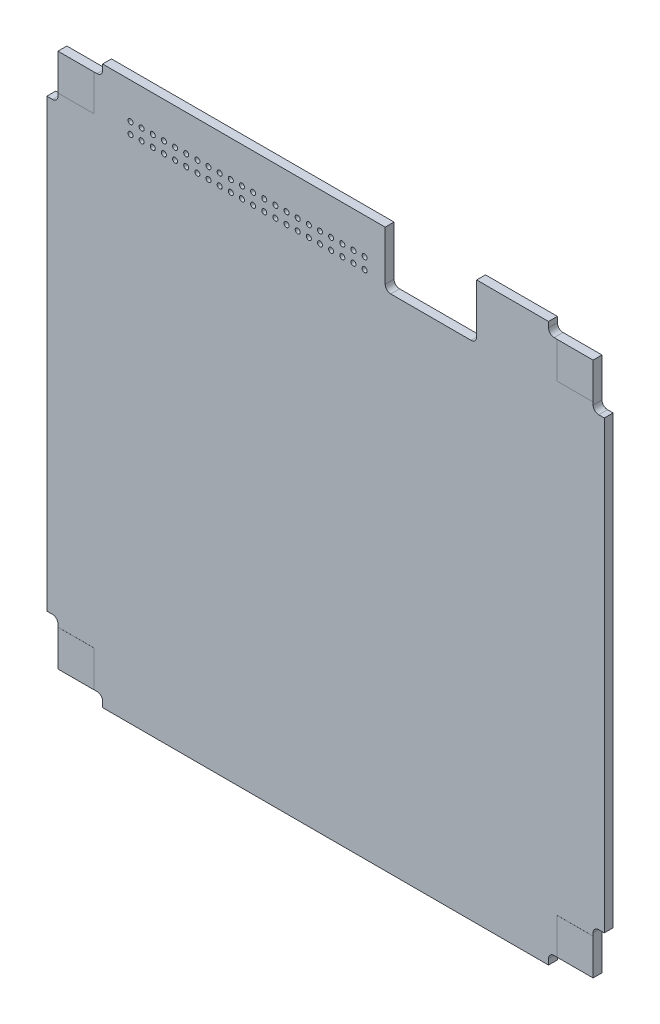
SolidWorks part; units mm, degrees
material "ABS"
ref_plane "Front Plane" through (0, 0, 0) normal (0, 0, 1) x (1, 0, 0)
ref_plane "Top Plane" through (0, 0, 0) normal (0, 1, 0) x (1, 0, 0)
ref_plane "Right Plane" through (0, 0, 0) normal (1, 0, 0) x (0, 0, -1)
sketch "Sketch1" plane through (0, 0, 0) normal (0, 0, 1) x (1, 0, 0)
  line L0 (-40, 50) -> (-40, 48)
  line L1 (-50, -50) -> (50, -50)
  line L2 (-50, -50) -> (-50, 50)
  line L3 (-50, 50) -> (50, 50)
  line L4 (50, -50) -> (50, 50)
  line L5 (-50, -50) -> (50, 50) construction
  line L6 (-50, 50) -> (50, -50) construction
  line L7 (-50, 50) -> (-40, 50)
  line L8 (-50, 50) -> (-50, 40)
  line L9 (-40, 48) -> (-48, 48)
  line L10 (-48, 48) -> (-48, 40)
  line L11 (50, 50) -> (40, 50)
  line L12 (50, 50) -> (50, 40)
  line L13 (-48, 40) -> (-50, 40)
  line L14 (50, 40) -> (48, 40)
  line L15 (-50, -50) -> (-37.8649, -50)
  line L16 (-50, -50) -> (-50, -37.8649)
  line L17 (50, 50) -> (50, 40)
  line L18 (50, 50) -> (40, 50)
  line L19 (50, -50) -> (41.5, -50)
  line L20 (50, -50) -> (50, -41.5)
  line L21 (48, 40) -> (48, 48)
  line L22 (48, 48) -> (40, 48)
  line L23 (40, 48) -> (40, 50)
  line L24 (40, -50) -> (40, -48)
  line L25 (50, -50) -> (40, -50)
  line L26 (50, -50) -> (50, -40)
  line L27 (40, -48) -> (48, -48)
  line L28 (48, -48) -> (48, -40)
  line L29 (48, -40) -> (50, -40)
  line L30 (-50, -40) -> (-48, -40)
  line L31 (-50, -50) -> (-50, -40)
  line L32 (-50, -50) -> (-40, -50)
  line L33 (-48, -40) -> (-48, -48)
  line L34 (-48, -48) -> (-40, -48)
  line L35 (-40, -48) -> (-40, -50)
  point P0 (0, 0)
  point P38 (0, 0)
  dimension "D1" = 100
  dimension "D2" = 100
  dimension "D3" = 2
  dimension "D4" = 10
  dimension "D5" = 4
extrude "Boss-Extrude1" add sketch "Sketch1" along normal blind 1.5875 contours L1 L4 L3 L2 region at (0, 0, 0)
fillet "Fillet1" radius 1 8 edges at (-48, -40, 0.7937) (-40, -48, 0.7937) (40, -48, 0.7937) (48, -40, 0.7937) (48, 40, 0.7937) (40, 48, 0.7937) (-40, 48, 0.7937) (-48, 40, 0.7937)
sketch "Sketch2" plane through (0, 0, 1.5875) normal (0, 0, 1) x (1, 0, 0)
  line L0 (0, 50) -> (0, -50) construction
  line L1 (-40, 50) -> (40, 50) construction
  line L2 (-40, -50) -> (40, -50) construction
  line L4 (-36, 45.8) -> (8, 45.8) construction
  line L5 (-36, 45.8) -> (-36, 43.55) construction
  line L6 (-36, 43.55) -> (8, 43.55) construction
  line L7 (8, 45.8) -> (8, 43.55) construction
  line L8 (-36, 50) -> (8, 50) construction
  line L9 (-36, 50) -> (-36, 45.8) construction
  line L10 (-36, 45.8) -> (8, 45.8) construction
  line L11 (8, 50) -> (8, 45.8) construction
  circle A0 centre (-35, 43.55) radius 0.45
  circle A1 centre (-33, 43.55) radius 0.45
  circle A2 centre (-31, 43.55) radius 0.45
  circle A3 centre (-29, 43.55) radius 0.45
  circle A4 centre (-27, 43.55) radius 0.45
  circle A5 centre (-25, 43.55) radius 0.45
  circle A6 centre (-23, 43.55) radius 0.45
  circle A7 centre (-21, 43.55) radius 0.45
  circle A8 centre (-19, 43.55) radius 0.45
  circle A9 centre (-17, 43.55) radius 0.45
  circle A10 centre (-15, 43.55) radius 0.45
  circle A11 centre (-13, 43.55) radius 0.45
  circle A12 centre (-11, 43.55) radius 0.45
  circle A13 centre (-9, 43.55) radius 0.45
  circle A14 centre (-7, 43.55) radius 0.45
  circle A15 centre (-5, 43.55) radius 0.45
  circle A16 centre (-3, 43.55) radius 0.45
  circle A17 centre (-1, 43.55) radius 0.45
  circle A18 centre (1, 43.55) radius 0.45
  circle A19 centre (3, 43.55) radius 0.45
  circle A20 centre (5, 43.55) radius 0.45
  circle A21 centre (7, 43.55) radius 0.45
  circle A22 centre (-33, 41.55) radius 0.45
  circle A23 centre (-31, 41.55) radius 0.45
  circle A24 centre (-29, 41.55) radius 0.45
  circle A25 centre (-27, 41.55) radius 0.45
  circle A26 centre (-25, 41.55) radius 0.45
  circle A27 centre (-23, 41.55) radius 0.45
  circle A28 centre (-21, 41.55) radius 0.45
  circle A29 centre (-19, 41.55) radius 0.45
  circle A30 centre (-17, 41.55) radius 0.45
  circle A31 centre (-15, 41.55) radius 0.45
  circle A32 centre (-13, 41.55) radius 0.45
  circle A33 centre (-11, 41.55) radius 0.45
  circle A34 centre (-9, 41.55) radius 0.45
  circle A35 centre (-7, 41.55) radius 0.45
  circle A36 centre (-5, 41.55) radius 0.45
  circle A37 centre (-3, 41.55) radius 0.45
  circle A38 centre (-1, 41.55) radius 0.45
  circle A39 centre (1, 41.55) radius 0.45
  circle A40 centre (3, 41.55) radius 0.45
  circle A41 centre (5, 41.55) radius 0.45
  circle A42 centre (7, 41.55) radius 0.45
  circle A43 centre (-35, 41.55) radius 0.45
  dimension "D1" = 0.9
  dimension "D6" = 15
  dimension "D4" = 42
  dimension "D5" = 2
  dimension "D7" = 2.25
  dimension "D8" = 44
  dimension "D10" = 1
  dimension "D11" = 4.2
  dimension "D2" = 22
  dimension "D3" = 2
extrude "Cut-Extrude1" cut sketch "Sketch2" against normal through all
sketch "Sketch3" plane through (0, 50, 0) normal (0, 1, 0) x (1, 0, 0)
  line L0 (-40, 0) -> (40, 0) construction
  line L1 (10.7, 0) -> (19.7, 0)
  line L2 (10.7, 0) -> (10.7, -1.5875)
  line L3 (10.7, -1.5875) -> (19.7, -1.5875)
  line L5 (-40, -1.5875) -> (40, -1.5875) construction
  line L6 (15.2, 0) -> (15.2, -1.5875) construction
  line L7 (12, 0) -> (12, -1.5875) construction
  line L8 (18.4, 0) -> (18.4, -1.5875) construction
  line L9 (-40, -1.5875) -> (40, -1.5875) construction
  line L10 (7, 0) -> (7, -1.5875) construction
  line L11 (6.55, -1.5875) -> (7.45, -1.5875) construction
  line L12 (19.7, 0) -> (27.1, 0)
  line L14 (19.7, -1.5875) -> (27.1, -1.5875)
  line L15 (27.1, 0) -> (27.1, -1.5875)
  dimension "D1" = 9
  dimension "D2" = 6.4
  dimension "D3" = 3.2
  dimension "D4" = 5
  dimension "D5" = 7.4
extrude "Cut-Extrude2" cut sketch "Sketch3" against normal blind 9.8806
fillet "Fillet2" radius 1 2 edges at (10.7, 40.1194, 0.7938) (27.1, 40.1194, 0.7937)
sketch "Sketch4" plane through (0, 0, 1.5875) normal (0, 0, 1) x (1, 0, 0)
  line L1 (-48, 48) -> (-41.5, 48)
  line L2 (-48, 48) -> (-48, 41.5)
  line L3 (-48, 41.5) -> (-41.5, 41.5)
  line L4 (-41.5, 48) -> (-41.5, 41.5)
  line L5 (-48, -48) -> (-41.5, -48)
  line L6 (-48, -48) -> (-48, -41.5)
  line L7 (-48, -41.5) -> (-41.5, -41.5)
  line L8 (-41.5, -48) -> (-41.5, -41.5)
  line L9 (48, -48) -> (41.5, -48)
  line L10 (48, -48) -> (48, -41.5)
  line L11 (48, -41.5) -> (41.5, -41.5)
  line L12 (41.5, -48) -> (41.5, -41.5)
  line L13 (48, 48) -> (41.5, 48)
  line L14 (48, 48) -> (48, 41.5)
  line L15 (48, 41.5) -> (41.5, 41.5)
  line L16 (41.5, 48) -> (41.5, 41.5)
  dimension "D1" = 6.5
extrude "Boss-Extrude2" add sketch "Sketch4" along normal blind 0.01
